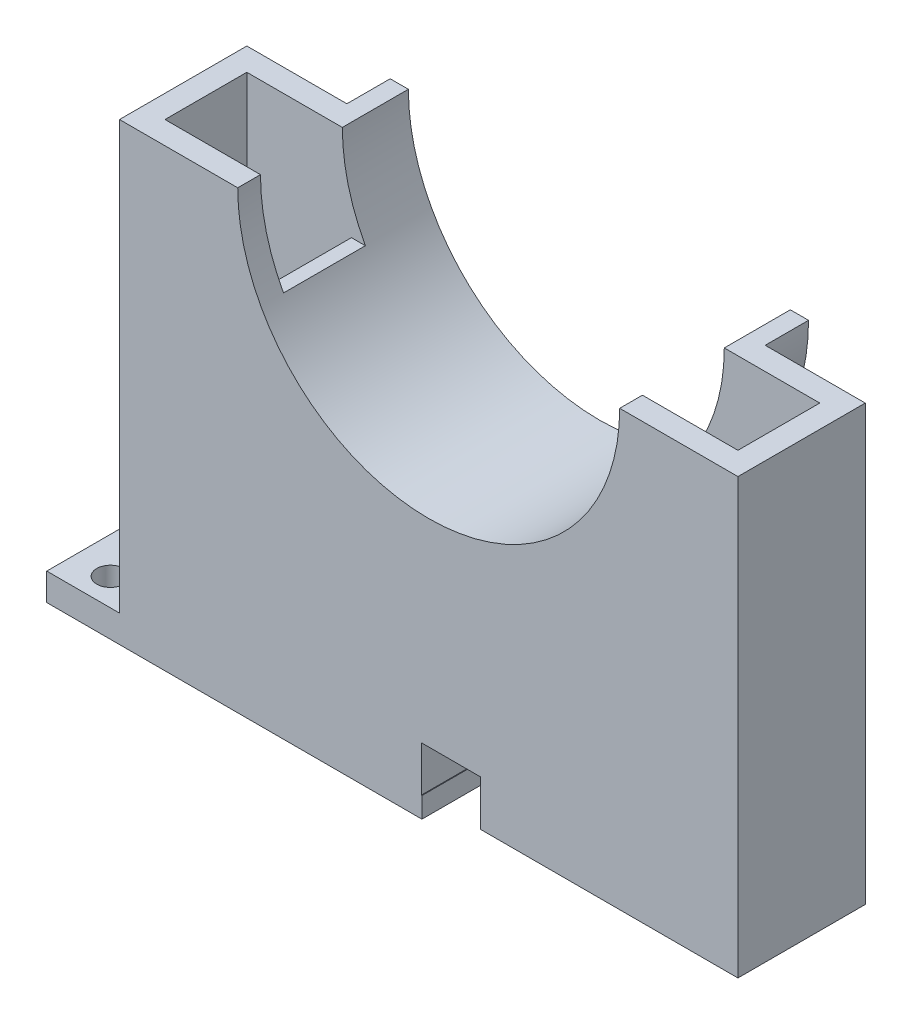
SolidWorks part; units mm, degrees
ref_plane "Front Plane" through (0, 0, 0) normal (0, 0, 1) x (1, 0, 0)
ref_plane "Top Plane" through (0, 0, 0) normal (0, 1, 0) x (1, 0, 0)
ref_plane "Right Plane" through (0, 0, 0) normal (1, 0, 0) x (0, 0, -1)
sketch "Sketch1" plane through (0, 0, 0) normal (0, 0, 1) x (1, 0, 0)
  line L0 (0, 0) -> (0, 3)
  line L1 (0, 3) -> (8, 3)
  line L2 (0, 0) -> (76, 0)
  line L3 (76, 0) -> (76, 50)
  line L4 (8, 3) -> (8, 50)
  line L5 (8, 50) -> (21, 50)
  line L6 (76, 50) -> (63, 50)
  arc A1 (63, 50) -> (21, 50) centre (42, 50) cw
  dimension "D1" = 76
  dimension "D2" = 21
  dimension "D3" = 3
  dimension "D4" = 50
  dimension "D5" = 8
extrude "Boss-Extrude1" add sketch "Sketch1" along normal blind 14
sketch "Sketch2" plane through (0, 0, 0) normal (0, -1, 0) x (1, 0, 0)
  line L0 (42, 14) -> (42, 0) construction
  line L1 (0, 14) -> (76, 14) construction
  line L2 (0, 0) -> (76, 0) construction
  line L3 (63, 14) -> (21, 14) construction
  line L4 (73.5, 11.5) -> (62, 11.5)
  line L5 (62, 11.5) -> (62, 2.5)
  line L6 (62, 2.5) -> (73.5, 2.5)
  line L7 (73.5, 2.5) -> (73.5, 11.5)
  line L10 (76, 14) -> (76, 0) construction
  line L11 (22, 2.5) -> (10.5, 2.5)
  line L12 (22, 11.5) -> (22, 2.5)
  line L13 (10.5, 11.5) -> (22, 11.5)
  line L14 (10.5, 2.5) -> (10.5, 11.5)
  point P14 (76, 7)
  point P15 (73.5, 7)
  dimension "D1" = 11.5
  dimension "D2" = 9
  dimension "D3" = 2.5
extrude "Cut-Extrude1" cut sketch "Sketch2" against normal up to surface (50 mm away) up to face at (14.5, 50, 7)
sketch "Sketch3" plane through (0, 3, 0) normal (0, 1, 0) x (1, 0, 0)
  line L0 (4, -3) -> (4, -11) construction
  line L1 (0, -14) -> (0, 0) construction
  line L4 (8, -14) -> (0, -14) construction
  circle A0 centre (4, -3) radius 1.5
  circle A1 centre (4, -11) radius 1.5
  point P7 (4, -14)
  point P10 (0, -7)
  point P11 (4, -7)
  dimension "D1" = 3
  dimension "D2" = 3
  dimension "D3" = 8
extrude "screw holes" cut sketch "Sketch3" against normal up to surface (3 mm away) up to face at (67.75, 0, 7)
sketch "Sketch4" plane through (0, 50, 0) normal (0, 1, 0) x (1, 0, 0)
  line L0 (8, -14) -> (76, -14) construction
  line L1 (10.5, -11.5) -> (73.5, -11.5)
  line L5 (73.5, -2.5) -> (73.5, -11.5)
  line L9 (10.5, -2.5) -> (10.5, -11.5)
  line L10 (10.5, -2.5) -> (73.5, -2.5)
  line L11 (10.5, -2.5) -> (10.5, -11.5) construction
extrude "Cut-Extrude2" cut sketch "Sketch4" against normal blind 10
sketch "Sketch5" plane through (0, 0, 0) normal (0, 0, -1) x (-1, 0, 0)
  line L0 (-76, 0) -> (-76, 2.25)
  line L1 (-76, 0) -> (-76, 50) construction
  line L2 (-76, 2.25) -> (-41.255, 2.25)
  line L3 (-41.255, 2.25) -> (-41.255, 0)
  line L4 (0, 0) -> (-76, 0) construction
  line L5 (-41.255, 0) -> (-76, 0)
  arc A1 (-63, 50) -> (-21, 50) centre (-42, 50) ccw construction
  point P12 (-42, 29)
  dimension "D1" = 2.25
  dimension "D2" = 0.745
extrude "Cut-Extrude3" cut sketch "Sketch5" against normal up to surface (14 mm away) up to face at (31.5, 23.125, 14)
sketch "Sketch6" plane through (0, 0, 14) normal (0, 0, 1) x (1, 0, 0)
  line L0 (41.18, 2.25) -> (47.68, 2.25)
  line L2 (76, 2.25) -> (41.255, 2.25) construction
  line L3 (41.255, 2.25) -> (41.255, 0) construction
  line L4 (47.68, 2.25) -> (47.68, 7.25)
  line L5 (47.68, 7.25) -> (41.18, 7.25)
  line L6 (41.18, 7.25) -> (41.18, 2.25)
  point P6 (44.43, 2.25)
  dimension "D1" = 6.5
  dimension "D2" = 3.175
  dimension "D3" = 5
extrude "Cut-Extrude4" cut sketch "Sketch6" against normal up to surface (14 mm away) up to face at (33.451, 18.95, 0)
sketch "Sketch7" plane through (0, 0, 14) normal (0, 0, 1) x (1, 0, 0)
  line L0 (21, 50) -> (19, 50)
  line L1 (21, 50) -> (8, 50) construction
  line L2 (63, 50) -> (65, 50)
  line L3 (76, 50) -> (63, 50) construction
  arc A0 (21, 50) -> (63, 50) centre (42, 50) ccw
  arc A1 (19, 50) -> (65, 50) centre (42, 50) ccw
  dimension "D1" = 2
  dimension "D2" = 2
extrude "Boss-Extrude2" add sketch "Sketch7" against normal blind 4.7625 from surface starting at face at (36.5879, 14.8929, 0)
